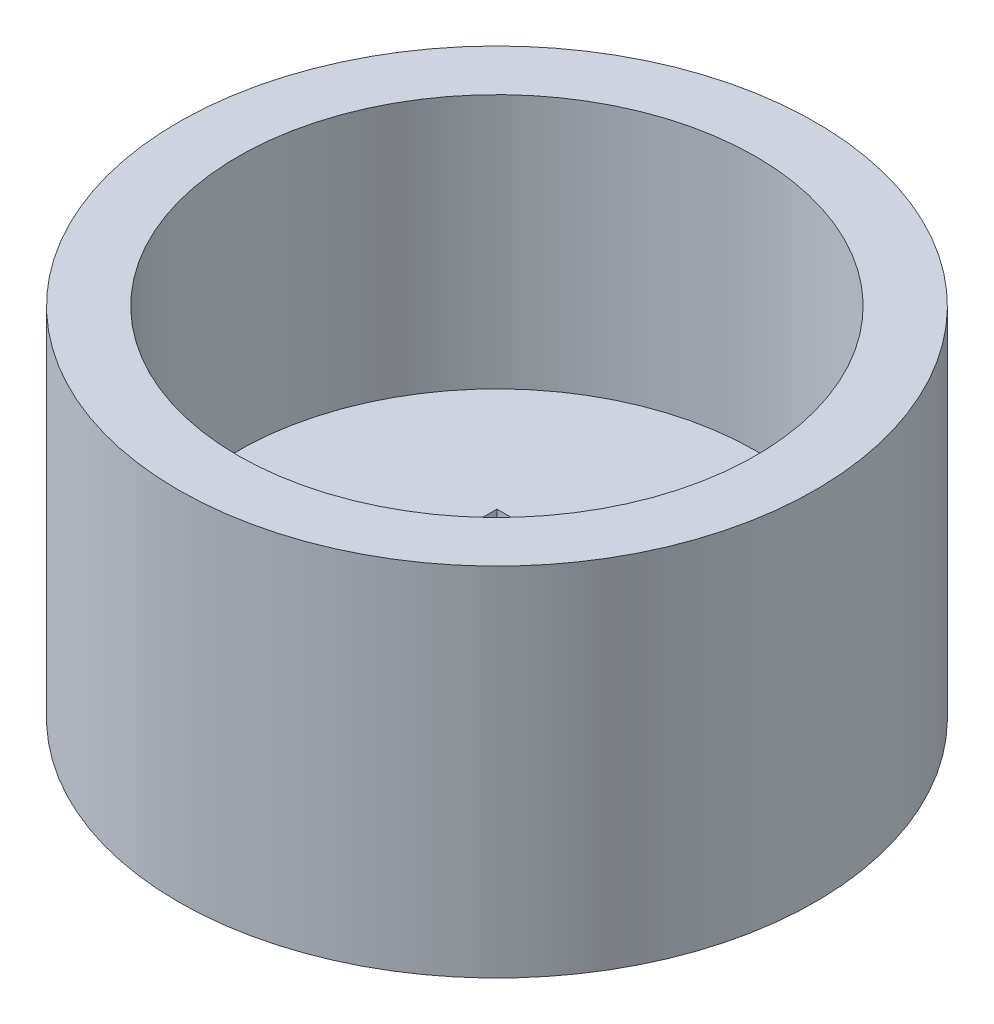
SolidWorks part; units mm, degrees
ref_plane "Front Plane" through (0, 0, 0) normal (0, 0, 1) x (1, 0, 0)
ref_plane "Top Plane" through (0, 0, 0) normal (0, 1, 0) x (1, 0, 0)
ref_plane "Right Plane" through (0, 0, 0) normal (1, 0, 0) x (0, 0, -1)
sketch "Sketch1" plane through (0, 0, 0) normal (0, 1, 0) x (1, 0, 0)
  circle A0 centre (0, 0) radius 25
  circle A1 centre (0, 0) radius 20.325
  dimension "D1" = 50
  dimension "D2" = 40.65
extrude "Boss-Extrude1" add sketch "Sketch1" along normal blind 20
extrude "Boss-Extrude2" add sketch "Sketch1<2>" against normal blind 8 contours A0
sketch "Sketch1<2>" plane through (0, 0, 0) normal (0, 1, 0) x (1, 0, 0) same geometry as "Sketch1"
sketch "Sketch3" plane through (0, -8, 0) normal (0, -1, 0) x (1, 0, 0)
  line L0 (0, 0) -> (0, -22) construction
  line L1 (6.2, 21.1) -> (-6.2, 21.1)
  line L2 (6.2, 21.1) -> (6.2, -11)
  line L3 (6.2, -11) -> (-6.2, -11)
  line L4 (-6.2, 21.1) -> (-6.2, -11)
  line L5 (6.2, 16.3) -> (-6.2, 16.3)
  line L6 (6.2, -6.2) -> (-6.2, -6.2)
  circle A0 centre (0, -8.6) radius 1.325
  circle A1 centre (0, 18.7) radius 1.325
  circle A2 centre (0, 0) radius 25 construction
  point P13 (0, -11)
  dimension "D2" = 2.65
  dimension "D3" = 2.65
  dimension "D1" = 27.3
  dimension "D4" = 18.7
  dimension "D5" = 32.1
  dimension "D6" = 12.4
  dimension "D7" = 2.4
  dimension "D8" = 4.8
  dimension "D9" = 4.8
extrude "Cut-Extrude1" cut sketch "Sketch3" against normal blind 2.7 contours L5 L2 L1 L4 A1 | L6 L0 A0 L3 L2 | L0 L6 L4 L3 A0 region at (3.3592, -8, -8.6) region at (-3.3592, -8, -8.6) region at (0, -8, 16.433)
extrude "Cut-Extrude3" cut sketch "Sketch3<4>" against normal blind 44.7 contours L6 L2 L5 L4 region at (0, -8, 5.05)
sketch "Sketch3<4>" plane through (0, -8, 0) normal (0, -1, 0) x (1, 0, 0) same geometry as "Sketch3"
extrude "Cut-Extrude4" cut sketch "Sketch3<5>" against normal blind 38.7 contours A1 | A0 L0 | L0 A0 region at (0.5623, -8, -8.6) region at (-0.5623, -8, -8.6) region at (0, -8, 18.7)
sketch "Sketch3<5>" plane through (0, -8, 0) normal (0, -1, 0) x (1, 0, 0) same geometry as "Sketch3"
